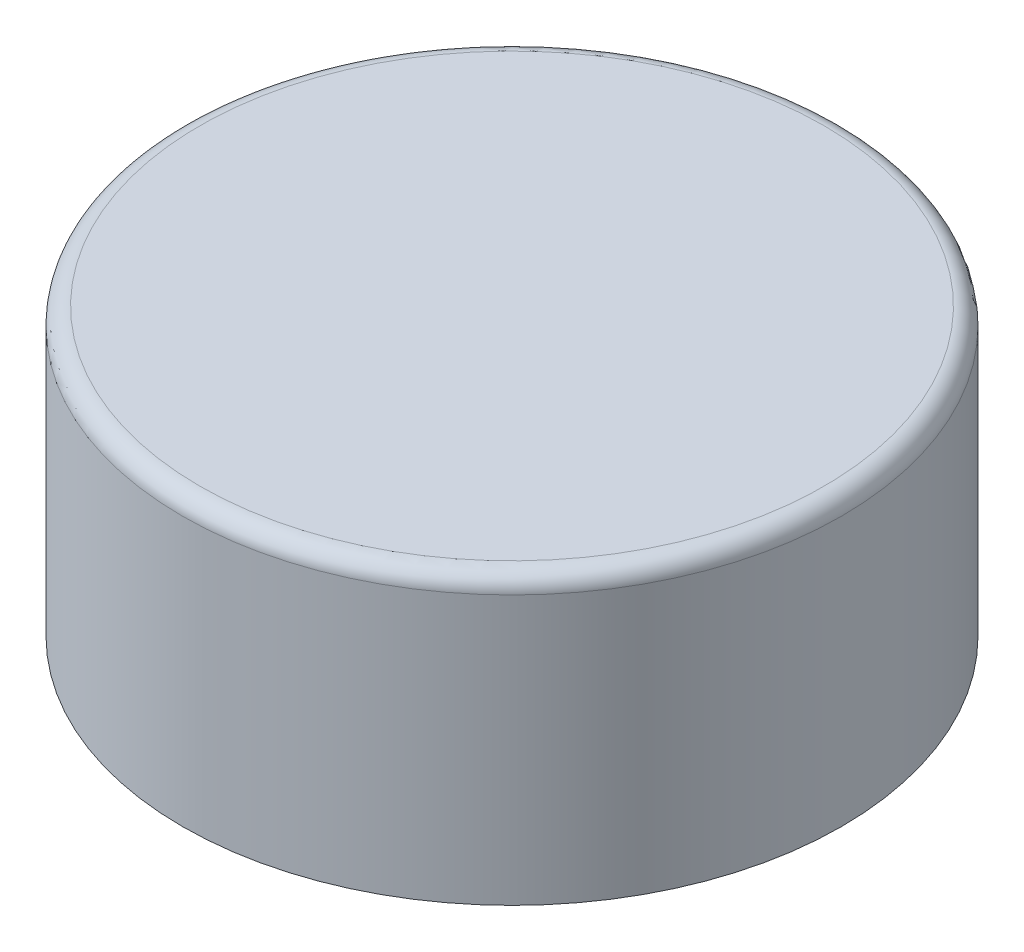
SolidWorks part; units mm, degrees
material "Polyetheretherketone (PEEK)"
ref_plane "Front Plane" through (0, 0, 0) normal (0, 0, 1) x (1, 0, 0)
ref_plane "Top Plane" through (0, 0, 0) normal (0, 1, 0) x (1, 0, 0)
ref_plane "Right Plane" through (0, 0, 0) normal (1, 0, 0) x (0, 0, -1)
sketch "Sketch1" plane through (0, 0, 0) normal (0, 1, 0) x (1, 0, 0)
  circle A0 centre (0, 0) radius 19
  circle A1 centre (0, 0) radius 18.1
  dimension "D1" = 36.2
  dimension "D2" = 38
extrude "Boss-Extrude1" add sketch "Sketch1" along normal blind 15
sketch "Sketch2" plane through (0, 0, 0) normal (0, 0, 1) x (1, 0, 0)
  line L0 (0, 0) -> (-18.1, 0) construction
  line L1 (-18.1, 0) -> (-18.1, 1.8)
  line L2 (-18.1, 15) -> (-18.1, 0) construction
  line L3 (-18.1, 1.8) -> (-17.15, 1.3)
  line L4 (-18.1, -1.8) -> (-17.15, -1.3)
  line L5 (-18.1, -1.8) -> (-18.1, 0)
  line L6 (-17.15, 1.3) -> (-17.15, -1.3)
  dimension "D1" = 1.8
  dimension "D2" = 1.8
  dimension "D3" = 0.95
  dimension "D4" = 0.5
  dimension "D6" = 0.5
ref_plane "Plane1" through (0, 0, 0) normal (0, -1, 0) x (-1, 0, 0)
sketch "Sketch3" plane through (0, 0, 0) normal (0, -1, 0) x (-1, 0, 0)
  circle A0 centre (0, 0) radius 17
curve "Helix/Spiral1" pitch 3.75 height 15 radius 17 centre (0, 0, 0) axis (0, 1, 0) start towards (0, 0, -1)
sweep "Sweep1" add profiles "Sketch2" path "Helix/Spiral1"
ref_plane "Plane2" through (0, 15, 0) normal (0, 1, 0) x (1, 0, 0)
other "SurfaceCut1" flip cut yes
other "SurfaceCut2" flip cut yes
sketch "Sketch5" plane through (0, 15, 0) normal (0, 1, 0) x (1, 0, 0)
  circle A0 centre (0, 0) radius 19
  dimension "D1" = 38
extrude "Boss-Extrude2" add sketch "Sketch5" along normal blind 1.5
fillet "Fillet1" radius 1 1 edges at (0, 16.5, 19)
